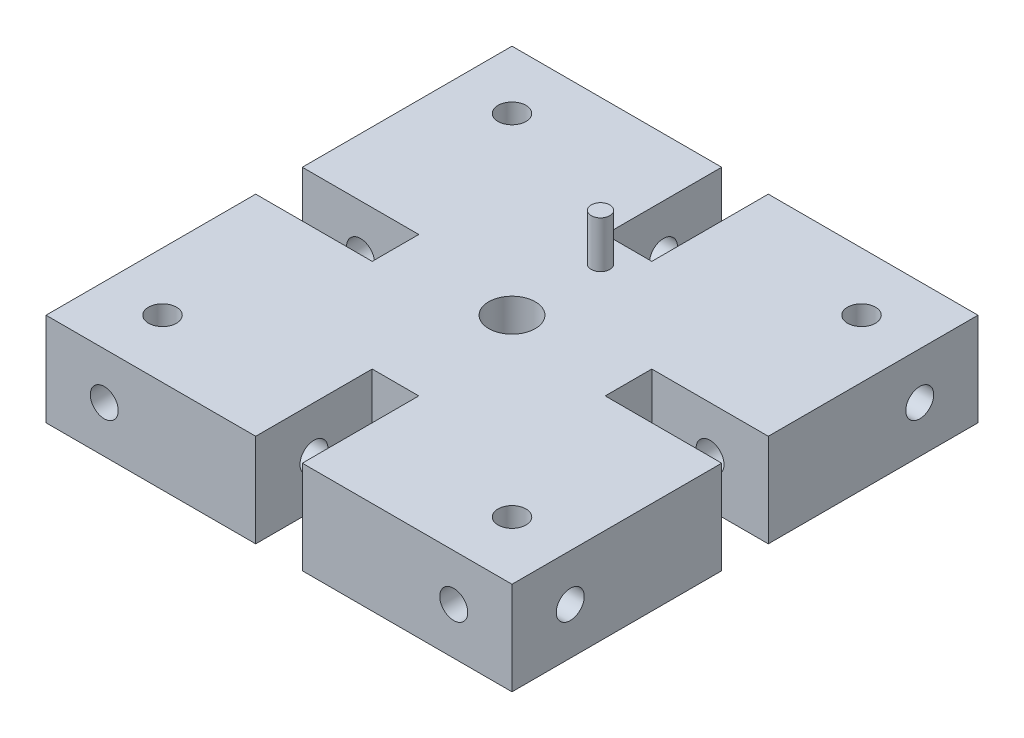
SolidWorks part; units mm, degrees
ref_plane "Front Plane" through (0, 0, 0) normal (0, 0, 1) x (1, 0, 0)
ref_plane "Top Plane" through (0, 0, 0) normal (0, 1, 0) x (1, 0, 0)
ref_plane "Right Plane" through (0, 0, 0) normal (1, 0, 0) x (0, 0, -1)
sketch "Sketch1" plane through (0, 0, 0) normal (0, 1, 0) x (1, 0, 0)
  line L0 (-7.5, 12.5) -> (-7.5, 25)
  line L1 (12.5, -12.5) -> (-12.5, -12.5)
  line L2 (12.5, -12.5) -> (12.5, 12.5)
  line L3 (12.5, 12.5) -> (-12.5, 12.5)
  line L4 (-12.5, -12.5) -> (-12.5, 12.5)
  line L5 (12.5, -12.5) -> (-12.5, 12.5) construction
  line L6 (12.5, 12.5) -> (-12.5, -12.5) construction
  line L7 (-7.5, 25) -> (-2.5, 25)
  line L8 (-2.5, 25) -> (-2.5, 12.5)
  line L9 (0, -1000) -> (0, 49000) construction
  line L10 (-1000, 0) -> (49000, 0) construction
  line L11 (2.5, 25) -> (2.5, 12.5)
  line L12 (7.5, 25) -> (2.5, 25)
  line L13 (7.5, 12.5) -> (7.5, 25)
  line L14 (7.5, -12.5) -> (7.5, -25)
  line L15 (7.5, -25) -> (2.5, -25)
  line L16 (2.5, -25) -> (2.5, -12.5)
  line L17 (-2.5, -25) -> (-2.5, -12.5)
  line L18 (-7.5, -25) -> (-2.5, -25)
  line L19 (-7.5, -12.5) -> (-7.5, -25)
  line L20 (12.5, 7.5) -> (25, 7.5)
  line L21 (25, 7.5) -> (25, 2.5)
  line L22 (25, 2.5) -> (12.5, 2.5)
  line L23 (12.5, -7.5) -> (25, -7.5)
  line L24 (25, -2.5) -> (12.5, -2.5)
  line L25 (25, -7.5) -> (25, -2.5)
  line L26 (-12.5, -7.5) -> (-25, -7.5)
  line L27 (-25, -7.5) -> (-25, -2.5)
  line L28 (-25, -2.5) -> (-12.5, -2.5)
  line L29 (-25, 2.5) -> (-12.5, 2.5)
  line L30 (-25, 7.5) -> (-25, 2.5)
  line L31 (-12.5, 7.5) -> (-25, 7.5)
  line L33 (25, -25) -> (-25, -25)
  line L34 (25, -25) -> (25, 25)
  line L35 (25, 25) -> (-25, 25)
  line L36 (-25, -25) -> (-25, 25)
  line L37 (25, -25) -> (-25, 25) construction
  line L38 (25, 25) -> (-25, -25) construction
  point P0 (0, 0)
  point P42 (0, 0)
  point P47 (-32.1475, 32.1475)
  dimension "D1" = 25
  dimension "D2" = 12.5
  dimension "D3" = 5
  dimension "D4" = 5
  dimension "D5" = 12.5
  dimension "D6" = 5
  dimension "D7" = 5
  dimension "D8" = 50
extrude "Boss-Extrude1" add sketch "Sketch1" along normal blind 10 contours L36 L31 L4 L3 L0 L35 | L8 L7 L0 L3 | L3 L13 L12 L11 | L34 L35 L13 L3 L2 L20 | L22 L21 L20 L2 | L23 L25 L24 L2 | L33 L34 L23 L2 L1 L14 | L16 L15 L14 L1 | L1 L19 L18 L17 | L36 L33 L19 L1 L4 L26 | L28 L27 L26 L4 | L4 L31 L30 L29 | L4 L1 L2 L3 L31 region at (-16.8056, 0, -16.8056) region at (-5, 0, -18.75) region at (0, 0, 0) region at (5, 0, -18.75) region at (-18.75, 0, -5) region at (16.8056, 0, -16.8056) region at (-18.75, 0, 5) region at (18.75, 0, -5) region at (-16.8056, 0, 16.8056) region at (18.75, 0, 5) region at (-5, 0, 18.75) region at (16.8056, 0, 16.8056) region at (5, 0, 18.75)
sketch "Sketch3" plane through (-2.5, 0, 0) normal (-1, 0, 0) x (0, 0, 1)
  line L3 (-25, 10) -> (-25, 0) construction
  line L4 (-2.5, 10) -> (-25, 10) construction
  circle A0 centre (-18.75, 5) radius 1.5
  point P2 (-18.75, 5)
  point P3 (0, 0)
  point P4 (-18.75, 4.9392)
  point P6 (-19.6813, 5.1434)
  point P11 (0, 0)
  point P12 (0, 0)
  point P14 (0, 0)
  dimension "D1" = 3
  dimension "D2" = 6.25
  dimension "D3" = 5
extrude "Cut-Extrude1" cut sketch "Sketch3" against normal through all both and the other way through all
mirror "Mirror1" about plane through (0, 0, 0) normal (0, 0, 1) of "Cut-Extrude1"
sketch "Sketch4" plane through (0, 0, 2.5) normal (0, 0, 1) x (1, 0, 0)
  line L2 (-25, 10) -> (-2.5, 10) construction
  line L3 (-25, 10) -> (-25, 0) construction
  circle A0 centre (-18.75, 5) radius 1.5
  point P5 (0, 0)
  dimension "D1" = 3
  dimension "D2" = 5
  dimension "D3" = 6.25
extrude "Cut-Extrude2" cut sketch "Sketch4" against normal through all both and the other way through all
mirror "Mirror2" about plane through (0, 0, 0) normal (1, 0, 0) of "Cut-Extrude2"
sketch "Sketch5" plane through (0, 10, 0) normal (0, 1, 0) x (1, 0, 0)
  circle A0 centre (0, 0) radius 2.5
  dimension "D1" = 5
extrude "Cut-Extrude3" cut sketch "Sketch5" against normal blind 10
sketch "Sketch6" plane through (0, 10, 0) normal (0, 1, 0) x (1, 0, 0)
  line L0 (2.5, 12.5) -> (-2.5, 12.5) construction
  circle A0 centre (0, 9.5) radius 1
  dimension "D1" = 2
  dimension "D2" = 3
extrude "Boss-Extrude2" add sketch "Sketch6" along normal blind 5
sketch "Sketch9" plane through (0, 10, 0) normal (0, 1, 0) x (1, 0, 0)
  line L1 (18.75, -18.75) -> (-18.75, -18.75) construction
  line L2 (18.75, -18.75) -> (18.75, 18.75) construction
  line L3 (18.75, 18.75) -> (-18.75, 18.75) construction
  line L4 (-18.75, -18.75) -> (-18.75, 18.75) construction
  line L5 (18.75, -18.75) -> (-18.75, 18.75) construction
  line L6 (18.75, 18.75) -> (-18.75, -18.75) construction
  line L7 (-25, 25) -> (-2.5, 25) construction
  line L8 (-25, 2.5) -> (-25, 25) construction
  circle A0 centre (-18.75, 18.75) radius 1.5
  circle A1 centre (18.75, 18.75) radius 1.5
  circle A2 centre (18.75, -18.75) radius 1.5
  circle A3 centre (-18.75, -18.75) radius 1.5
  point P0 (0, 0)
  dimension "D3" = 3
  dimension "D1" = 6.25
  dimension "D2" = 6.25
extrude "Cut-Extrude4" cut sketch "Sketch9" against normal through all
